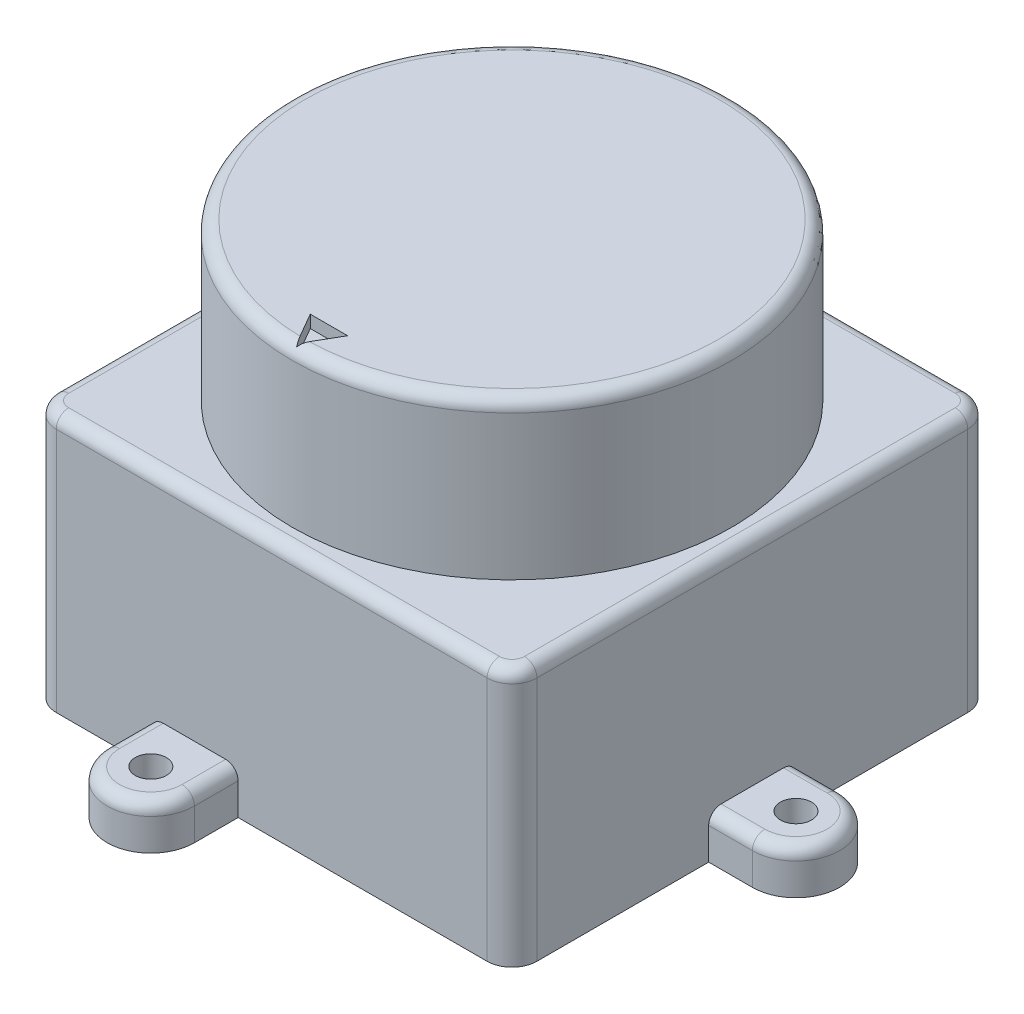
SolidWorks part; units mm, degrees
ref_plane "Front Plane" through (0, 0, 0) normal (0, 0, 1) x (1, 0, 0)
ref_plane "Top Plane" through (0, 0, 0) normal (0, 1, 0) x (1, 0, 0)
ref_plane "Right Plane" through (0, 0, 0) normal (1, 0, 0) x (0, 0, -1)
sketch "Sketch1" plane through (0, 0, 0) normal (0, 1, 0) x (1, 0, 0)
  line L1 (0, 0) -> (38.59, 0)
  line L2 (0, 0) -> (0, 38.59)
  line L3 (0, 38.59) -> (38.59, 38.59)
  line L4 (38.59, 0) -> (38.59, 38.59)
  dimension "D1" = 38.59
extrude "Boss-Extrude1" add sketch "Sketch1" along normal blind 20.7
draft "Draft1" [suppressed] type of draft neutral plane draft angle 2 faces to draft 4 reverse direction yes parameters "D1"=2
sketch "Sketch2" plane through (0, 20.7, 0) normal (0, 1, 0) x (1, 0, 0)
  line L0 (0, 38.59) -> (38.59, 0) construction
  circle A0 centre (19.295, 19.295) radius 17.645
  dimension "D1" = 35.29
extrude "Boss-Extrude2" add sketch "Sketch2" along normal blind 12.6
sketch "Sketch3" plane through (0, 33.3, 0) normal (0, 1, 0) x (1, 0, 0)
  line L0 (17.795, 4.5981) -> (19.295, 2)
  line L1 (19.295, 2) -> (20.795, 4.5981)
  line L2 (20.795, 4.5981) -> (17.795, 4.5981)
  line L3 (19.295, 38.59) -> (19.295, 2) construction
  line L4 (38.59, 38.59) -> (0, 38.59) construction
  line L5 (0, 0) -> (38.59, 0) construction
  dimension "D1" = 2
  dimension "D2" = 3
extrude "Cut-Extrude1" cut sketch "Sketch3" against normal blind 1
sketch "Sketch6" plane through (0, 0, 0) normal (1, 0, 0) x (0, 0, -1)
  line L0 (38.59, 0) -> (23.295, 1) construction
  line L1 (23.295, 5) -> (15.295, 5)
  line L2 (23.295, 5) -> (23.295, 1)
  line L3 (23.295, 1) -> (15.295, 1)
  line L4 (15.295, 5) -> (15.295, 1)
  line L5 (15.295, 1) -> (0, 0) construction
  line L6 (38.59, 0) -> (0, 0) construction
  dimension "D1" = 8
  dimension "D2" = 4
  dimension "D3" = 1
extrude "Cut-Extrude2" cut sketch "Sketch6" along normal blind 4
sketch "Sketch8" plane through (0, 0, 0) normal (0, -1, 0) x (1, 0, 0)
  line L0 (13.095, 3.505) -> (13.095, -42.095) construction
  line L1 (42.095, -19.295) -> (13.095, -19.295) construction
  line L2 (38.59, 0) -> (38.59, -38.59) construction
  line L3 (0, 0) -> (38.59, 0) construction
  line L4 (38.59, -38.59) -> (0, -38.59) construction
  line L5 (9.59, 3.505) -> (9.59, 0)
  line L6 (9.59, 0) -> (16.6, 0)
  line L7 (16.6, 0) -> (16.6, 3.505)
  line L8 (42.095, -15.79) -> (38.59, -15.79)
  line L9 (38.59, -15.79) -> (38.59, -22.8)
  line L10 (38.59, -22.8) -> (42.095, -22.8)
  line L11 (9.59, -42.095) -> (9.59, -38.59)
  line L12 (9.59, -38.59) -> (16.6, -38.59)
  line L13 (16.6, -38.59) -> (16.6, -42.095)
  circle A0 centre (13.095, 3.505) radius 3.505
  circle A1 centre (13.095, -42.095) radius 3.505
  circle A2 centre (42.095, -19.295) radius 3.505
  circle A3 centre (13.095, 3.505) radius 1.25
  circle A4 centre (42.095, -19.295) radius 1.25
  circle A5 centre (13.095, -42.095) radius 1.25
  point P8 (38.59, -19.295)
  line M10 (0, -38.59) -> (38.59, -38.59)
  line M11 (38.59, -38.59) -> (38.59, 0)
  line M12 (38.59, 0) -> (0, 0)
  dimension "D1" = 29
  dimension "D3" = 2.5
  dimension "D2" = 45.6
extrude "Boss-Extrude3" add sketch "Sketch8" against normal blind 3.55 contours A0 L5 L6 | A0 L7 M12 | A0 A3 | A2 L8 L9 | A2 L10 M11 | A2 A4 | A1 L11 M10 | A1 A5 | A1 L13 L12 region at (10.3729, 0, 0.7829) region at (15.8171, 0, -39.3729) region at (39.3729, 0, -16.5729) region at (13.095, 0, 6.9109) region at (15.8171, 0, 0.7829) region at (44.5033, 0, -16.8867) region at (39.3729, 0, -22.0171) region at (10.3729, 0, -39.3729) region at (15.5033, 0, -39.6867)
fillet "Fillet2" radius 2 4 edges at (0, 10.35, -38.59) (38.59, 10.35, -38.59) (38.59, 10.35, 0) (0, 10.35, 0)
fillet "Fillet1" radius 1 18 edges at (9.59, 3.55, -40.3425) (16.6, 3.55, -40.3425) (40.3425, 3.55, -22.8) (40.3425, 3.55, -15.79) (16.6, 3.55, 1.7525) (9.59, 3.55, 1.7525) (13.095, 3.55, -45.6) (45.6, 3.55, -19.295) (13.095, 3.55, 7.01) (38.0042, 20.7, -38.0042) (38.59, 20.7, -19.295) (38.0042, 20.7, -0.5858) (19.295, 20.7, 0) (0.5858, 20.7, -0.5858) (0, 20.7, -19.295) (0.5858, 20.7, -38.0042) (19.295, 33.3, -1.65) (19.295, 20.7, -38.59)
